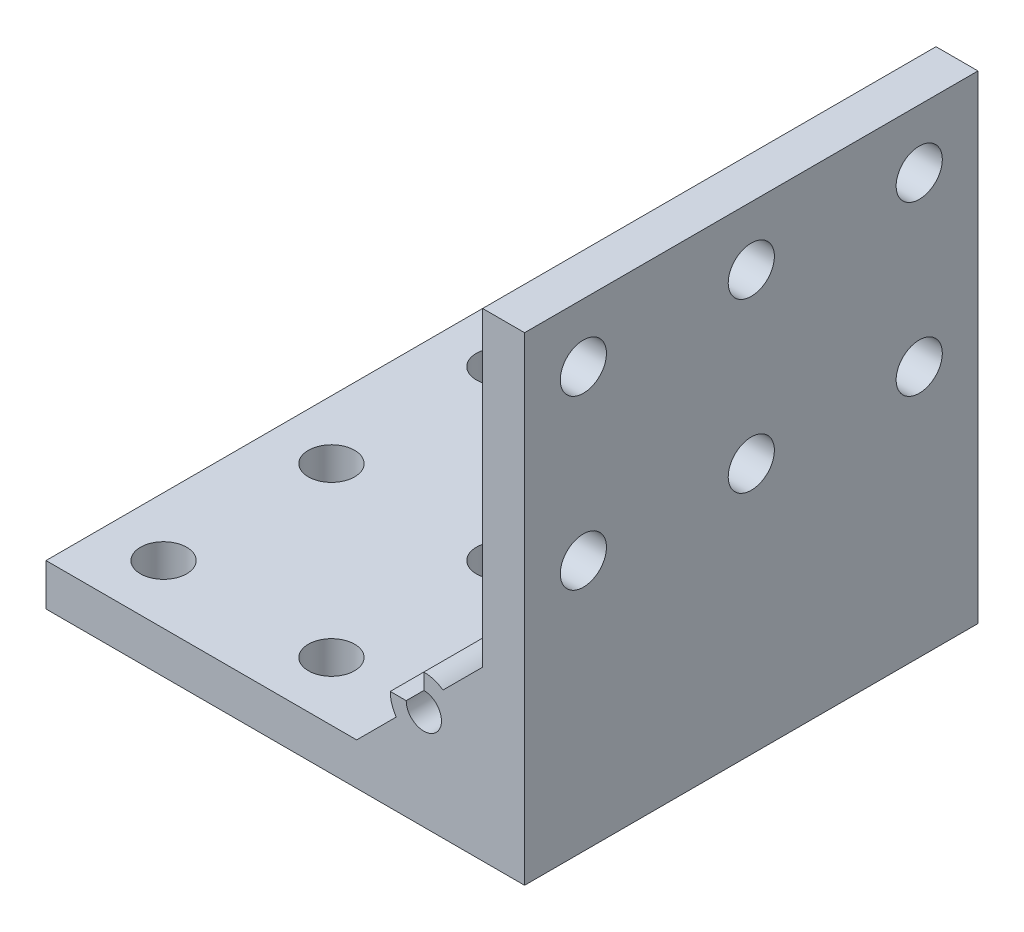
SolidWorks part; units mm, degrees
material "5052-O"
ref_plane "Front Plane" through (0, 0, 0) normal (0, 0, 1) x (1, 0, 0)
ref_plane "Top Plane" through (0, 0, 0) normal (0, 1, 0) x (1, 0, 0)
ref_plane "Right Plane" through (0, 0, 0) normal (1, 0, 0) x (0, 0, -1)
sketch "Sketch1" plane through (0, 0, 0) normal (0, 0, 1) x (1, 0, 0)
  line L0 (-8, -7) -> (-3.2839, -2.2839)
  line L1 (7, 8) -> (7, 45)
  line L2 (7, 45) -> (12, 45)
  line L3 (12, 45) -> (12, -12)
  line L4 (12, -12) -> (-45, -12)
  line L5 (-45, -12) -> (-45, -7)
  line L6 (-45, -7) -> (-8, -7)
  line L7 (12, -12) -> (-45, 45) construction
  line L8 (2.2839, 3.2839) -> (7, 8)
  line L9 (0, 2.1) -> (0, 4)
  line L10 (-2.1, 0) -> (-4, 0)
  arc A0 (-2.1, 0) -> (0, 2.1) centre (0, 0) ccw
  arc A1 (2.2839, 3.2839) -> (0, 4) centre (0, 0) ccw
  arc A2 (-4, 0) -> (-3.2839, -2.2839) centre (0, 0) ccw
  dimension "D1" = 4.2
  dimension "D5" = 8
  dimension "D2" = 57
  dimension "D3" = 12
  dimension "D4" = 5
  dimension "D6" = 20
extrude "Boss-Extrude1" add sketch "Sketch1" against normal blind 27 and the other way blind 27
sketch "Sketch2" plane through (12, 0, 0) normal (1, 0, 0) x (0, 0, -1)
  line L0 (0, 0) -> (0, 38) construction
  line L1 (-20, 38) -> (20, 38) construction
  line L2 (-20, 18) -> (-20, 38) construction
  line L3 (20, 18) -> (20, 38) construction
  line L4 (-20, 18) -> (20, 18) construction
  line L5 (-27, -12) -> (27, -12) construction
  circle A0 centre (-20, 38) radius 2.75
  circle A1 centre (0, 38) radius 2.75
  circle A2 centre (20, 38) radius 2.75
  circle A3 centre (-20, 18) radius 2.75
  circle A4 centre (0, 18) radius 2.75
  circle A5 centre (20, 18) radius 2.75
  dimension "D3" = 5.5
  dimension "D1" = 30
  dimension "D2" = 20
  dimension "D4" = 20
extrude "Cut-Extrude1" cut sketch "Sketch2" against normal up to next
sketch "Sketch3" plane through (0, -12, 0) normal (0, -1, 0) x (1, 0, 0)
  line L0 (0, 0) -> (-38, 0) construction
  line L1 (-38, -20) -> (-38, 20) construction
  line L2 (-18, -20) -> (-18, 20) construction
  line L3 (-38, 20) -> (-18, 20) construction
  line L4 (-38, -20) -> (-18, -20) construction
  line L5 (12, 27) -> (12, -27) construction
  circle A0 centre (-38, -20) radius 2.75
  circle A1 centre (-38, 0) radius 2.75
  circle A2 centre (-38, 20) radius 2.75
  circle A3 centre (-18, -20) radius 2.75
  circle A4 centre (-18, 0) radius 2.75
  circle A5 centre (-18, 20) radius 2.75
  dimension "D1" = 5.5
  dimension "D2" = 20
  dimension "D3" = 20
  dimension "D4" = 30
extrude "Cut-Extrude2" cut sketch "Sketch3" against normal up to next
